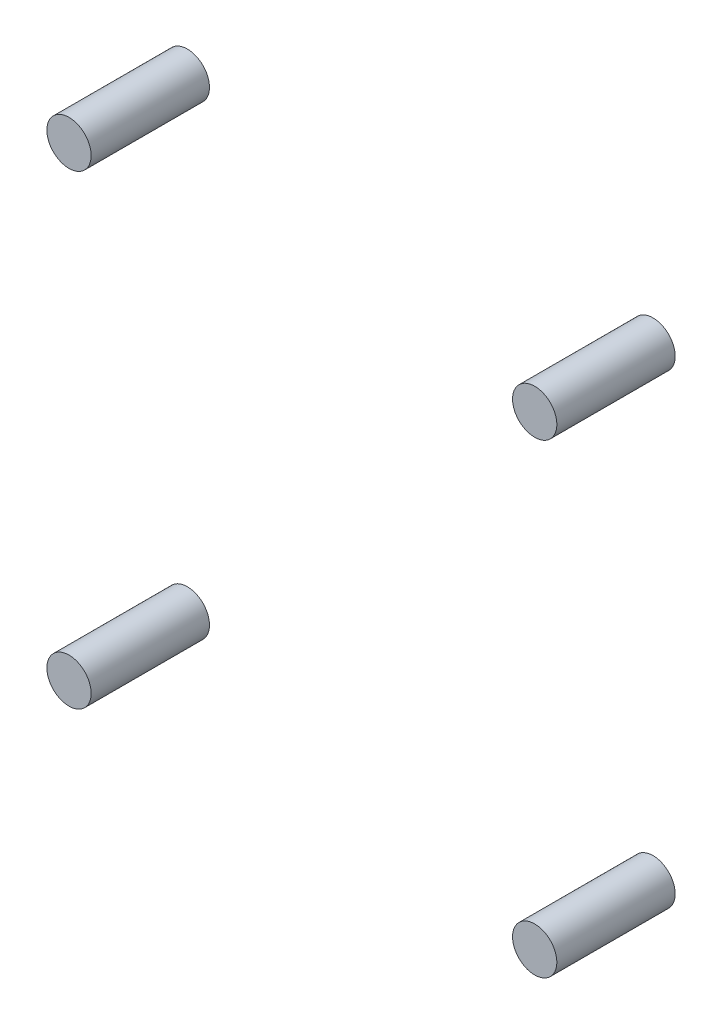
SolidWorks part; units mm, degrees
ref_plane "Front Plane" through (0, 0, 0) normal (0, 0, 1) x (1, 0, 0)
ref_plane "Top Plane" through (0, 0, 0) normal (0, 1, 0) x (1, 0, 0)
ref_plane "Right Plane" through (0, 0, 0) normal (1, 0, 0) x (0, 0, -1)
sketch "Sketch1" plane through (0, 0, 0) normal (0, 0, 1) x (1, 0, 0)
  line L0 (-32.6579, 32.6579) -> (32.6579, -32.6579) construction
  circle A4 centre (32.6579, -32.6579) radius 3.1044
  circle A5 centre (-32.6579, 32.6579) radius 3.1044
  circle A6 centre (-32.6579, -32.6579) radius 3.1044
  circle A7 centre (32.6579, 32.6579) radius 3.1044
  point P21 (0, 0)
extrude "Boss-Extrude1" add sketch "Sketch1" along normal blind 16.6
